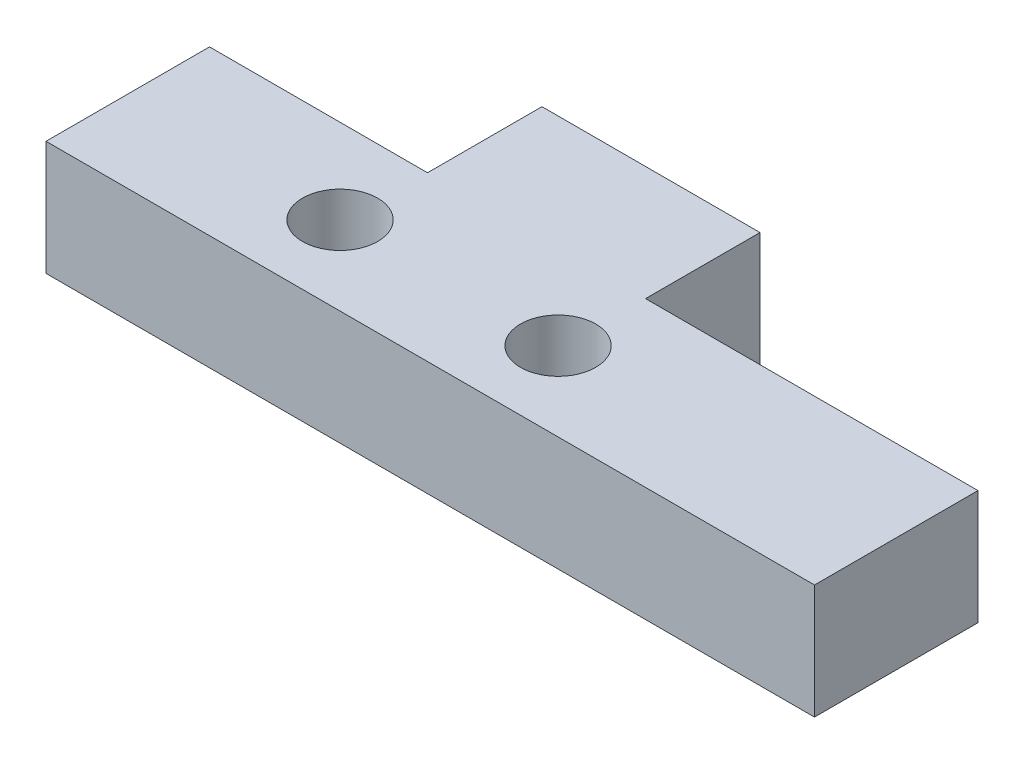
SolidWorks part; units mm, degrees
ref_plane "Front Plane" through (0, 0, 0) normal (0, 0, 1) x (1, 0, 0)
ref_plane "Top Plane" through (0, 0, 0) normal (0, 1, 0) x (1, 0, 0)
ref_plane "Right Plane" through (0, 0, 0) normal (1, 0, 0) x (0, 0, -1)
sketch "Sketch1" plane through (0, 0, 0) normal (0, 1, 0) x (1, 0, 0)
  line L1 (-15.24, -3.81) -> (15.24, -3.81)
  line L2 (-15.24, -3.81) -> (-15.24, 3.81)
  line L3 (-15.24, 3.81) -> (15.24, 3.81)
  line L4 (15.24, -3.81) -> (15.24, 3.81)
  line L5 (-15.24, -3.81) -> (15.24, 3.81) construction
  line L6 (-15.24, 3.81) -> (15.24, -3.81) construction
  point P0 (0, 0)
  dimension "D1" = 7.62
  dimension "D2" = 30.48
extrude "Boss-Extrude1" add sketch "Sketch1" along normal mid plane 5.334
sketch "Sketch2" plane through (0, 2.667, 0) normal (0, 1, 0) x (1, 0, 0)
  line L0 (15.24, 3.81) -> (-15.24, 3.81) construction
  line L1 (-5.08, 3.81) -> (5.08, 3.81)
  line L2 (-5.08, 3.81) -> (-5.08, 9.144)
  line L3 (-5.08, 9.144) -> (5.08, 9.144)
  line L4 (5.08, 3.81) -> (5.08, 9.144)
  line L5 (-15.24, 3.81) -> (-5.08, 3.81) construction
  line L6 (5.08, 3.81) -> (15.24, 3.81) construction
  dimension "material" = 5.334
extrude "Boss-Extrude2" add sketch "Sketch2" against normal blind 5.334
sketch "Sketch3" plane through (0, 2.667, 0) normal (0, 1, 0) x (1, 0, 0)
  line L1 (15.24, 3.81) -> (20.574, 3.81)
  line L2 (15.24, 3.81) -> (15.24, -3.81)
  line L3 (15.24, -3.81) -> (20.574, -3.81)
  line L4 (20.574, 3.81) -> (20.574, -3.81)
  dimension "material" = 5.334
extrude "Boss-Extrude3" add sketch "Sketch3" against normal blind 5.334
sketch "Sketch6" plane through (0, -2.667, 0) normal (0, -1, 0) x (1, 0, 0)
  circle A0 centre (4.9416, 0.127) radius 1.7526 construction
  circle A1 centre (-5.2184, 0.127) radius 1.7526 construction
  circle A2 centre (4.9416, 0.127) radius 1.7526
  circle A3 centre (-5.2184, 0.127) radius 1.7526
extrude "Cut-Extrude1" cut sketch "Sketch6" against normal through all
equation "\"material\"=\"GMaterial@Platform.assembly\""
equation "\"D1@Boss-Extrude1\"=\"material\""
equation "\"D1@Boss-Extrude2\"=\"material\""
equation "\"D1@Boss-Extrude3\"=\"material\""
